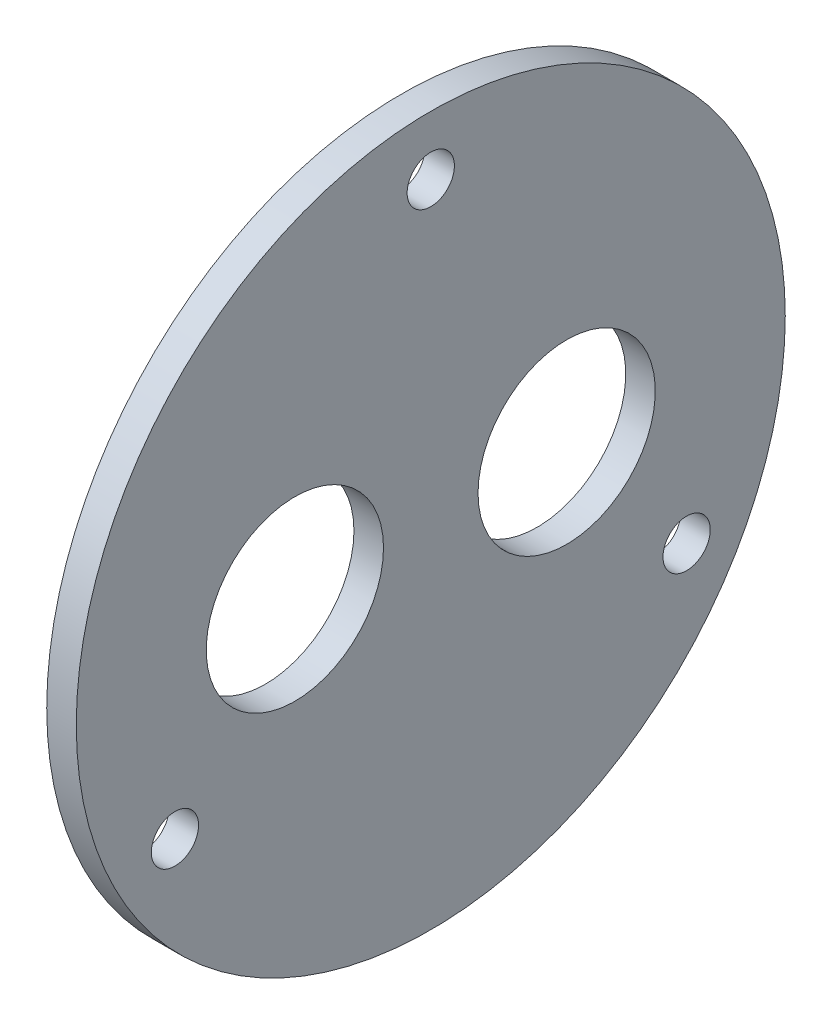
SolidWorks part; units mm, degrees
ref_plane "Front Plane" through (0, 0, 0) normal (0, 0, 1) x (1, 0, 0)
ref_plane "Top Plane" through (0, 0, 0) normal (0, 1, 0) x (1, 0, 0)
ref_plane "Right Plane" through (0, 0, 0) normal (1, 0, 0) x (0, 0, -1)
sketch "Sketch1" plane through (0, 0, 0) normal (1, 0, 0) x (0, 0, -1)
  line L0 (0, 71.6561) -> (0, -95.6447) construction
  line L1 (-75.2705, 0) -> (80.9544, 0) construction
  circle A0 centre (0, 0) radius 60
  circle A1 centre (0, 50) radius 4
  circle A2 centre (43.3013, -25) radius 4
  circle A3 centre (-43.3013, -25) radius 4
  circle A4 centre (-23, 0) radius 15
  circle A5 centre (23, 0) radius 15
  point P14 (0, 0)
  dimension "D1" = 120
  dimension "D2" = 8
  dimension "D5" = 30
  dimension "D3" = 50
  dimension "D6" = 23
  dimension "D4" = 3
extrude "Boss-Extrude1" add sketch "Sketch1" along normal blind 5
